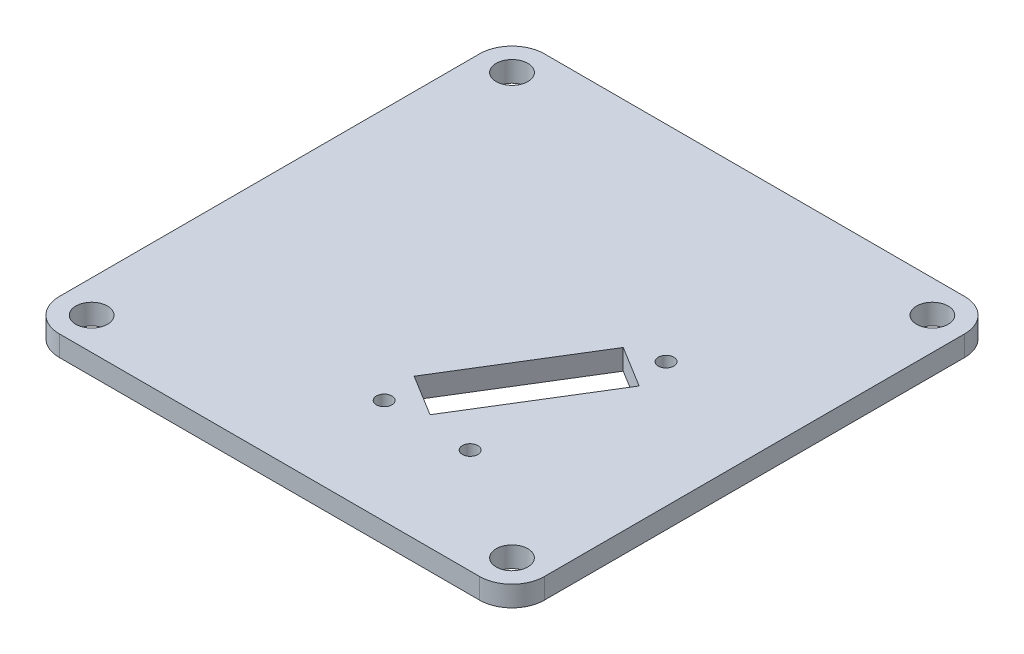
SolidWorks part; units mm, degrees
ref_plane "Front Plane" through (0, 0, 0) normal (0, 0, 1) x (1, 0, 0)
ref_plane "Top Plane" through (0, 0, 0) normal (0, 1, 0) x (1, 0, 0)
ref_plane "Right Plane" through (0, 0, 0) normal (1, 0, 0) x (0, 0, -1)
sketch "Sketch1" plane through (0, 0, 0) normal (0, 1, 0) x (1, 0, 0)
  line L1 (10, 0) -> (140, 0)
  line L2 (0, 10) -> (0, 140)
  line L3 (10, 150) -> (140, 150)
  line L4 (150, 10) -> (150, 140)
  arc A0 (140, 0) -> (150, 10) centre (140, 10) ccw
  arc A1 (10, 0) -> (0, 10) centre (10, 10) cw
  arc A2 (0, 140) -> (10, 150) centre (10, 140) cw
  arc A3 (140, 150) -> (150, 140) centre (140, 140) cw
  point P7 (150, 0)
  point P10 (0, 0)
  point P13 (0, 150)
  point P16 (150, 150)
  dimension "D3" = 10
  dimension "D1" = 150
  dimension "D2" = 150
extrude "Boss-Extrude1" add sketch "Sketch1" along normal blind 6.35
sketch "Sketch2" plane through (0, 6.35, 0) normal (0, 1, 0) x (1, 0, 0)
  line L0 (73.7734, 30) -> (106.7734, 30) construction
  line L1 (106.7734, 30) -> (115, 97) construction
  line L2 (115, 97) -> (73.7734, 30) construction
  line L3 (140, 150) -> (10, 150) construction
  line L4 (0, 140) -> (0, 10) construction
  line L5 (76.2218, 43.5199) -> (88.997, 35.659)
  line L6 (88.997, 35.659) -> (113.6278, 75.6881)
  line L7 (113.6278, 75.6881) -> (100.8525, 83.5489)
  line L8 (76.2218, 43.5199) -> (100.8525, 83.5489)
  line L9 (10, 0) -> (140, 0) construction
  line L10 (150, 10) -> (150, 140) construction
  circle A0 centre (78.0682, 32.4) radius 2.4
  circle A1 centre (104.6501, 32.4) radius 2.4
  circle A2 centre (111.2767, 86.3694) radius 2.4
  circle A3 centre (10, 140) radius 4.9
  circle A4 centre (10, 10) radius 4.9
  circle A5 centre (140, 140) radius 4.9
  circle A6 centre (140, 10) radius 4.9
  dimension "D6" = 4.8
  dimension "D7" = 4.8
  dimension "D8" = 4.8
  dimension "D14" = 9.8
  dimension "D15" = 9.8
  dimension "D16" = 9.8
  dimension "D17" = 9.8
  dimension "D20" = 10
  dimension "D1" = 97
  dimension "D2" = 33
  dimension "D3" = 67
  dimension "D4" = 30
  dimension "D5" = 35
  dimension "D9" = 15
  dimension "D10" = 47
  dimension "D11" = 5
  dimension "D12" = 7.865
  dimension "D13" = 8.503
  dimension "D18" = 10
  dimension "D19" = 10
  dimension "D21" = 10
  dimension "D22" = 10
  dimension "D23" = 10
  dimension "D24" = 10
  dimension "D25" = 10
extrude "Cut-Extrude1" cut sketch "Sketch2" against normal through all
sketch "Sketch4" plane through (0, 0, 0) normal (0, -1, 0) x (1, 0, 0)
  line L0 (88.5372, -63.5344) -> (101.3124, -55.6735) construction
  line L1 (100.8525, -83.5489) -> (76.2218, -43.5199) construction
  line L2 (88.997, -35.659) -> (113.6278, -75.6881) construction
